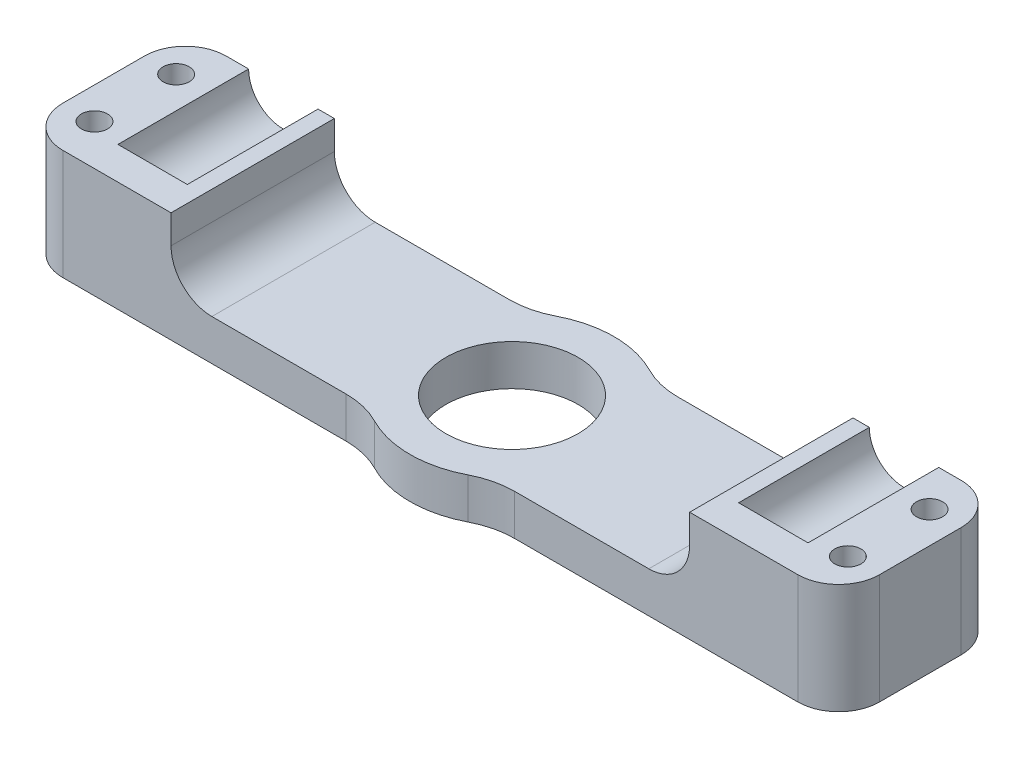
SolidWorks part; units mm, degrees
ref_plane "Front Plane" through (0, 0, 0) normal (0, 0, 1) x (1, 0, 0)
ref_plane "Top Plane" through (0, 0, 0) normal (0, 1, 0) x (1, 0, 0)
ref_plane "Right Plane" through (0, 0, 0) normal (1, 0, 0) x (0, 0, -1)
sketch "Sketch1" plane through (0, 0, 0) normal (0, 1, 0) x (1, 0, 0)
  line L0 (-44, 0) -> (-44, -44) construction
  line L1 (-44, -44) -> (44, -44) construction
  line L2 (44, -44) -> (44, 0) construction
  line L4 (-44, -10) -> (44, -10)
  line L5 (-44, -10) -> (-44, 10)
  line L6 (-44, 10) -> (44, 10)
  line L7 (44, -10) -> (44, 10)
  line L8 (-44, -10) -> (44, 10) construction
  line L9 (-44, 10) -> (44, -10) construction
  arc A0 (44, 0) -> (-44, 0) centre (0, 0) ccw construction
  dimension "D1" = 88
  dimension "D2" = 88
  dimension "D3" = 20
extrude "Boss-Extrude1" add sketch "Sketch1" along normal blind 27
sketch "Sketch2" plane through (0, 0, 10) normal (0, 0, 1) x (1, 0, 0)
  line L1 (-1044, 13.5) -> (48956, 13.5) construction
  line L2 (0, -1000) -> (0, 49000) construction
  line L3 (-44, 27) -> (-44, 0) construction
  circle A0 centre (-38, 13.5) radius 4.25
  circle A1 centre (38, 13.5) radius 4.25
  point P2 (-44, 13.5)
  dimension "D1" = 8.5
  dimension "D2" = 6
extrude "Cut-Extrude1" cut sketch "Sketch2" against normal through all
sketch "Sketch7" plane through (0, 27, 0) normal (0, 1, 0) x (1, 0, 0)
  circle A0 centre (0, 0) radius 12.5
  dimension "D1" = 25
extrude "Boss-Extrude2" add sketch "Sketch7" against normal up to surface (27 mm away) up to face at (0, 0, 0)
sketch "Sketch4" plane through (0, 27, 0) normal (0, 1, 0) x (1, 0, 0)
  circle A0 centre (0, 0) radius 8.1
  dimension "D1" = 16.2
extrude "Cut-Extrude3" cut sketch "Sketch4" against normal through all
fillet "Fillet2" radius 10 4 edges at (7.5, 13.5, 10) (-7.5, 13.5, 10) (7.5, 13.5, -10) (-7.5, 13.5, -10)
sketch "Sketch9" plane through (-44, 0, 0) normal (-1, 0, 0) x (0, 0, 1)
  line L5 (-1017.3065, 27) -> (48982.6935, 27) construction
  line L6 (-1016.9067, 13.5) -> (48983.0933, 13.5) construction
  line L7 (-12.5, 27) -> (-12.5, 0) construction
  line L8 (-10, 27) -> (10, 27) construction
  line L9 (12.5, 0) -> (12.5, 27) construction
  line L10 (-13.5, 27) -> (13.5, 27)
  line L11 (-13.5, 27) -> (-13.5, 13.5)
  line L12 (-13.5, 13.5) -> (13.5, 13.5)
  line L13 (13.5, 27) -> (13.5, 13.5)
  point P3 (-12.5, 13.5)
  dimension "D1" = 1
  dimension "D2" = 1
extrude "Cut-Extrude4" cut sketch "Sketch9" against normal through all
sketch "Sketch10" plane through (0, 0, 0) normal (0, 0, 1) x (1, 0, 0)
  line L0 (44, 0) -> (10.3078, 0) construction
  line L1 (31.75, 15.5) -> (-31.75, 15.5)
  line L2 (31.75, 15.5) -> (31.75, 5)
  line L3 (31.75, 5) -> (-31.75, 5)
  line L4 (-31.75, 15.5) -> (-31.75, 5)
  line L5 (10.3078, 13.5) -> (33.75, 13.5) construction
  dimension "D1" = 5
  dimension "D2" = 2
  dimension "D3" = 2
  dimension "D4" = 2
extrude "Cut-Extrude5" cut sketch "Sketch10" against normal through all and the other way through all
fillet "Fillet3" radius 5 2 edges at (-31.75, 5, 0) (31.75, 5, 0)
sketch "Sketch11" plane through (44, 0, 0) normal (1, 0, 0) x (0, 0, -1)
  line L4 (10, 0) -> (10, 13.5)
  line L5 (10, 13.5) -> (-10, 13.5)
  line L6 (-10, 13.5) -> (-10, 0)
  line L7 (-10, 0) -> (10, 0)
  line L8 (10, 0) -> (10, 13.5)
  line L9 (10, 13.5) -> (-10, 13.5)
  line L10 (-10, 13.5) -> (-10, 0)
  line L11 (-10, 0) -> (10, 0)
  dimension "D1" = 0
extrude "Boss-Extrude3" add sketch "Sketch11" along normal blind 6
sketch "Sketch12" plane through (0, 13.5, 0) normal (0, 1, 0) x (1, 0, 0)
  line L0 (46.125, -10) -> (46.125, 10) construction
  line L1 (50, -10) -> (42.25, -10) construction
  line L2 (42.25, 10) -> (50, 10) construction
  circle A0 centre (46.125, -5) radius 1.6
  circle A1 centre (46.125, 5) radius 1.6
  dimension "D1" = 3.2
  dimension "D2" = 5
  dimension "D3" = 5
extrude "Cut-Extrude6" cut sketch "Sketch12" against normal through all
mirror "Mirror1" about plane through (0, 0, 0) normal (1, 0, 0) of "Boss-Extrude3", "Cut-Extrude6"
fillet "Fillet4" radius 5 4 edges at (-50, 6.75, 10) (-50, 6.75, -10) (50, 6.75, 10) (50, 6.75, -10)
sketch "Sketch13" plane through (0, 0, 10) normal (0, 0, 1) x (1, 0, 0)
  line L0 (-42.25, 13.5) -> (-33.75, 13.5)
  line L1 (33.75, 13.5) -> (42.25, 13.5)
  arc A0 (33.75, 13.5) -> (42.25, 13.5) centre (38, 13.5) ccw construction
  arc A1 (-42.25, 13.5) -> (-33.75, 13.5) centre (-38, 13.5) ccw construction
  arc A2 (33.75, 13.5) -> (42.25, 13.5) centre (38, 13.5) ccw
  arc A3 (-42.25, 13.5) -> (-33.75, 13.5) centre (-38, 13.5) ccw
extrude "Boss-Extrude4" add sketch "Sketch13" against normal blind 4
